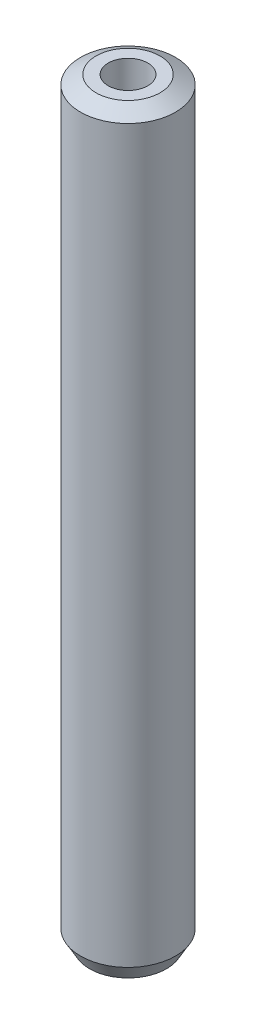
SolidWorks part; units mm, degrees
ref_plane "Front Plane" through (0, 0, 0) normal (0, 0, 1) x (1, 0, 0)
ref_plane "Top Plane" through (0, 0, 0) normal (0, 1, 0) x (1, 0, 0)
ref_plane "Right Plane" through (0, 0, 0) normal (1, 0, 0) x (0, 0, -1)
sketch "Sketch1" plane through (0, 0, 0) normal (0, 1, 0) x (1, 0, 0)
  circle A0 centre (0, 0) radius 15
  dimension "SHAFT_OD" = 30
extrude "Boss-Extrude1" add sketch "Sketch1" along normal blind 238.4937
sketch "Sketch2" plane through (0, 0, 0) normal (0, 1, 0) x (1, 0, 0)
  circle A0 centre (0, 0) radius 6.2437
  dimension "BORE_D" = 12.4875
extrude "Cut-Extrude1" cut sketch "Sketch2" along normal through all
chamfer "Chamfer1" distance 2.8317 angle 60 2 edges at (0, 238.4937, 15) (0, 0, 15) first distance on face at (0, 238.4937, 15) first distance on face at (0, 0, 6.2437)
